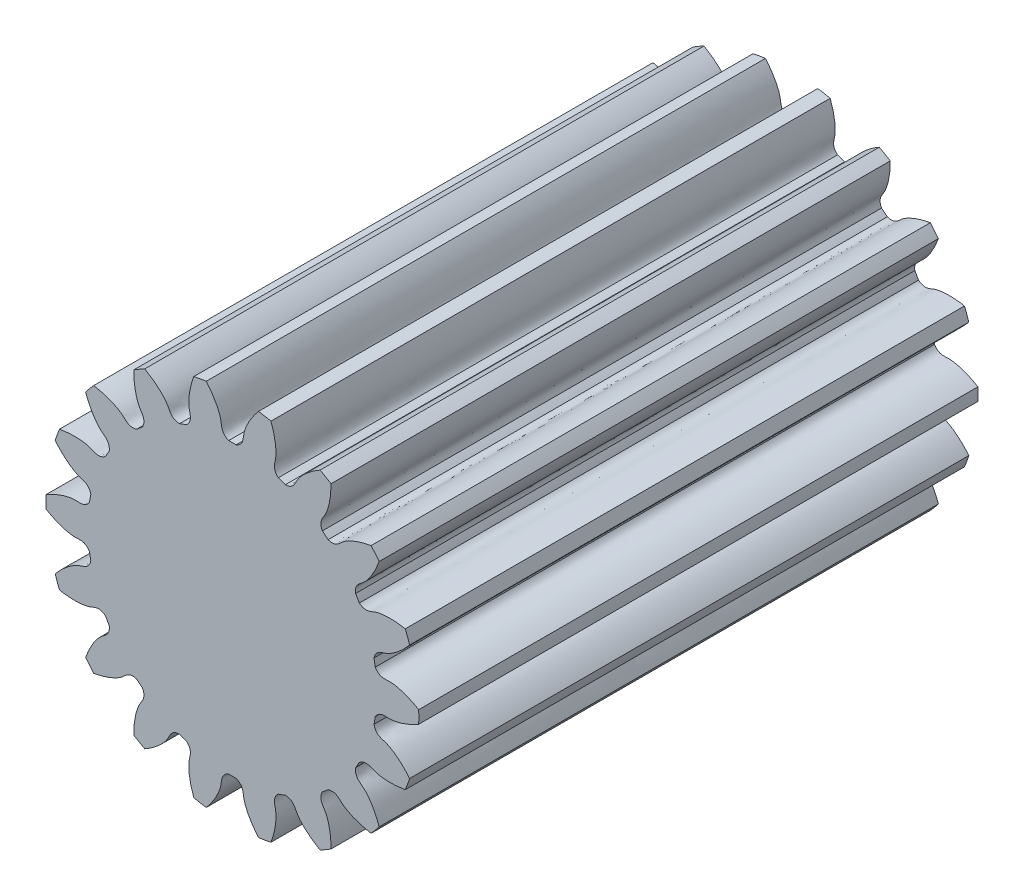
SolidWorks part; units mm, degrees
ref_plane "前视基准面" through (0, 0, 0) normal (0, 0, 1) x (1, 0, 0)
ref_plane "上视基准面" through (0, 0, 0) normal (0, 1, 0) x (1, 0, 0)
ref_plane "右视基准面" through (0, 0, 0) normal (1, 0, 0) x (0, 0, -1)
sketch "草图1" plane through (0, 0, 0) normal (0, 0, 1) x (1, 0, 0)
  circle A0 centre (0, 0) radius 10
extrude "凸台-拉伸1" add sketch "草图1" along normal blind 30
ref_axis "基准轴1" through (0, 0, -1.5) along (0, 0, 1)
sketch "草图2" plane through (0, 0, 0) normal (0, 0, 1) x (1, 0, 0)
  line L0 (0, 0) -> (0, 10) construction
  circle A0 centre (0, 0) radius 10 construction
  arc A1 (0.1994, 7.7474) -> (-0.1994, 7.7474) centre (0, 0) ccw
  arc A2 (3.0986, 11.3067) -> (-3.0986, 11.3067) centre (0, 0) ccw
  spline S0 degree 3 poles (0.1994, 7.7474) (0.6151, 7.9187) (0.5628, 8.2387) (0.6318, 8.5426) (0.6388, 8.5705) (0.6471, 8.6015) (0.657, 8.6357) (0.6686, 8.6728) (0.682, 8.7129) (0.6974, 8.7559) (0.7148, 8.8018) (0.7344, 8.8504) (0.7563, 8.9018) (0.7806, 8.9557) (0.8074, 9.0123) (0.8368, 9.0713) (0.869, 9.1328) (0.9041, 9.1965) (0.9421, 9.2625) (0.9831, 9.3305) (1.0273, 9.4006) (1.0748, 9.4727) (1.1256, 9.5465) (1.1799, 9.6221) (1.2377, 9.6993) (1.2991, 9.778) (1.3642, 9.858) (1.433, 9.9394) (1.5057, 10.0218) (1.5824, 10.1053) (1.663, 10.1897) (1.7477, 10.2749) (1.8365, 10.3607) (1.9295, 10.447) (2.0267, 10.5337) (2.1282, 10.6206) (2.234, 10.7076) (2.3442, 10.7946) (2.4588, 10.8814) (2.5779, 10.9679) (2.7015, 11.0539) (2.8741, 11.169) (3.0076, 11.2523) (3.0986, 11.3067) knots 0 0 0 0 0.187592 0.192996 0.199121 0.205966 0.213531 0.221818 0.230824 0.240552 0.250999 0.262168 0.274057 0.286666 0.299996 0.314047 0.328818 0.344309 0.360521 0.377454 0.395107 0.413481 0.432575 0.45239 0.472926 0.494181 0.516158 0.538855 0.562272 0.58641 0.611269 0.636848 0.663148 0.690168 0.717909 0.74637 0.775552 0.805454 0.836077 0.867421 0.899485 0.932269 1 1 1 1
  spline S1 degree 3 poles (-0.1994, 7.7474) (-0.6151, 7.9187) (-0.5628, 8.2387) (-0.6318, 8.5426) (-0.6388, 8.5705) (-0.6471, 8.6015) (-0.657, 8.6357) (-0.6686, 8.6728) (-0.682, 8.7129) (-0.6974, 8.7559) (-0.7148, 8.8018) (-0.7344, 8.8504) (-0.7563, 8.9018) (-0.7806, 8.9557) (-0.8074, 9.0123) (-0.8368, 9.0713) (-0.869, 9.1328) (-0.9041, 9.1965) (-0.9421, 9.2625) (-0.9831, 9.3305) (-1.0273, 9.4006) (-1.0748, 9.4727) (-1.1256, 9.5465) (-1.1799, 9.6221) (-1.2377, 9.6993) (-1.2991, 9.778) (-1.3642, 9.858) (-1.433, 9.9394) (-1.5057, 10.0218) (-1.5824, 10.1053) (-1.663, 10.1897) (-1.7477, 10.2749) (-1.8365, 10.3607) (-1.9295, 10.447) (-2.0267, 10.5337) (-2.1282, 10.6206) (-2.234, 10.7076) (-2.3442, 10.7946) (-2.4588, 10.8814) (-2.5779, 10.9679) (-2.7015, 11.0539) (-2.8741, 11.169) (-3.0076, 11.2523) (-3.0986, 11.3067) knots 0 0 0 0 0.187592 0.192996 0.199121 0.205966 0.213531 0.221818 0.230824 0.240552 0.250999 0.262168 0.274057 0.286666 0.299996 0.314047 0.328818 0.344309 0.360521 0.377454 0.395107 0.413481 0.432575 0.45239 0.472926 0.494181 0.516158 0.538855 0.562272 0.58641 0.611269 0.636848 0.663148 0.690168 0.717909 0.74637 0.775552 0.805454 0.836077 0.867421 0.899485 0.932269 1 1 1 1
extrude "切除-拉伸1" cut sketch "草图2" along normal through all
pattern_circular "阵列(圆周)1" count 18 every 20 about axis through (0, 0, -1.5) along (0, 0, 1) of "切除-拉伸1"
sketch "草图3" plane through (0, 0, 0) normal (0, 0, 1) x (1, 0, 0)
  circle A0 centre (0, 0) radius 9 construction
  dimension "Dn" = 18
